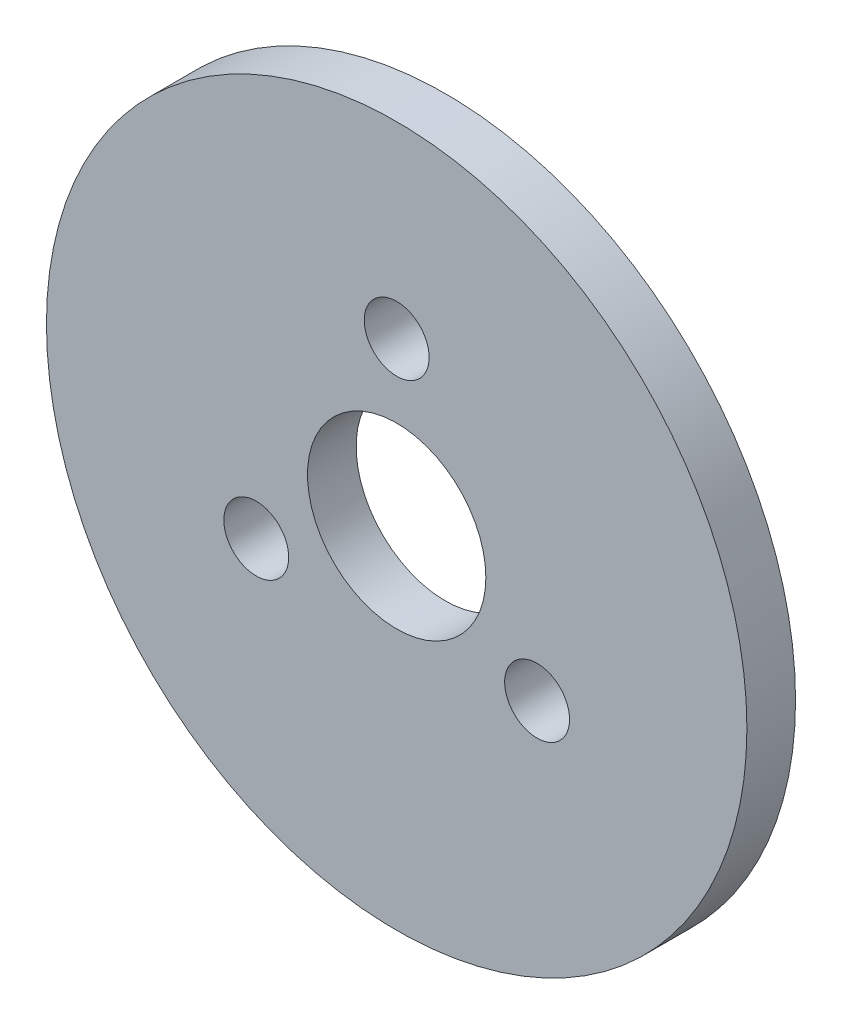
SolidWorks part; units mm, degrees
ref_plane "Front Plane" through (0, 0, 0) normal (0, 0, 1) x (1, 0, 0)
ref_plane "Top Plane" through (0, 0, 0) normal (0, 1, 0) x (1, 0, 0)
ref_plane "Right Plane" through (0, 0, 0) normal (1, 0, 0) x (0, 0, -1)
sketch "Sketch1" plane through (0, 0, 0) normal (0, 0, 1) x (1, 0, 0)
  circle A0 centre (0, 0) radius 21.6
  circle A1 centre (0, 0) radius 5.5
  dimension "D1" = 43.2
  dimension "D2" = 11
extrude "Boss-Extrude1" add sketch "Sketch1" along normal blind 3
sketch "Sketch2" plane through (0, 0, 3) normal (0, 0, 1) x (1, 0, 0)
  line L0 (0, 0) -> (0, 50000) construction
  line L1 (0, 0) -> (50000, 0) construction
  circle A0 centre (0, 10) radius 2
  circle A1 centre (0, 0) radius 5.5 construction
  circle A2 centre (8.6603, -5) radius 2
  circle A3 centre (-8.6603, -5) radius 2
  point P16 (0, 0)
  dimension "D1" = 4
  dimension "D2" = 10
  dimension "D3" = 3
extrude "Cut-Extrude1" cut sketch "Sketch2" against normal blind 3
